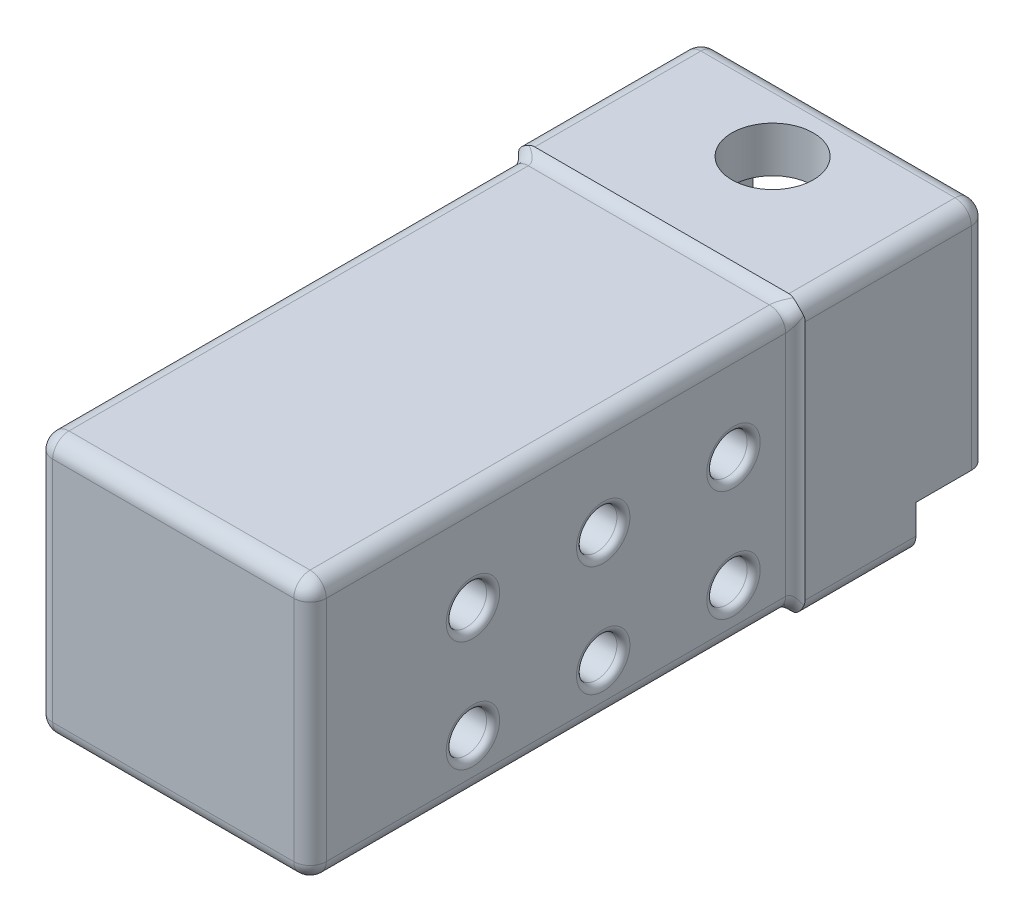
SolidWorks part; units mm, degrees
ref_plane "Front Plane" through (0, 0, 0) normal (0, 0, 1) x (1, 0, 0)
ref_plane "Top Plane" through (0, 0, 0) normal (0, 1, 0) x (1, 0, 0)
ref_plane "Right Plane" through (0, 0, 0) normal (1, 0, 0) x (0, 0, -1)
sketch "Sketch1" plane through (0, 0, 0) normal (0, 0, 1) x (1, 0, 0)
  line L0 (-4.572, -3.556) -> (4.572, -3.556)
  line L1 (-5.588, 5.334) -> (5.588, 5.334)
  line L2 (-5.588, 5.334) -> (-5.588, -5.334)
  line L3 (-5.588, -5.334) -> (5.588, -5.334)
  line L4 (5.588, 5.334) -> (5.588, -5.334)
  line L5 (-5.588, 5.334) -> (5.588, -5.334) construction
  line L6 (-5.588, -5.334) -> (5.588, 5.334) construction
  line L7 (4.572, -3.556) -> (4.572, -0.635)
  line L8 (4.572, -0.635) -> (3.556, -0.635)
  line L9 (3.556, -0.635) -> (3.556, 3.556)
  line L10 (3.556, 3.556) -> (-3.556, 3.556)
  line L11 (-3.556, 3.556) -> (-3.556, -0.635)
  line L12 (-3.556, -0.635) -> (-4.572, -0.635)
  line L13 (-4.572, -0.635) -> (-4.572, -3.556)
  point P5 (0, 3.556)
  point P7 (0, 0)
  dimension "D1" = 1.016
  dimension "D2" = 1.778
  dimension "D3" = 1.778
  dimension "D4" = 7.112
  dimension "D5" = 4.191
  dimension "D6" = 7.112
  dimension "D7" = 9.144
extrude "Boss-Extrude1" add sketch "Sketch1" along normal blind 7.112
sketch "Sketch2" plane through (0, 5.334, 0) normal (0, 1, 0) x (1, 0, 0)
  line L1 (5.588, 0) -> (-5.588, 0) construction
  circle A0 centre (0, -2.794) radius 1.5875
  dimension "D1" = 3.175
  dimension "D2" = 2.794
extrude "Cut-Extrude1" cut sketch "Sketch2" against normal through all both and the other way through all
sketch "Sketch3" plane through (0, 0, 7.112) normal (0, 0, 1) x (1, 0, 0)
  line L1 (-5.588, 5.334) -> (5.588, 5.334)
  line L2 (-5.588, 5.334) -> (-5.588, -5.334)
  line L3 (-5.588, -5.334) -> (5.588, -5.334)
  line L4 (5.588, 5.334) -> (5.588, -5.334)
sketch "Sketch7" plane through (0, 0, 7.112) normal (0, 0, 1) x (1, 0, 0)
  line L14 (-5.334, -5.08) -> (5.334, -5.08)
  line L15 (5.334, -5.08) -> (5.334, 5.08)
  line L16 (5.334, 5.08) -> (-5.334, 5.08)
  line L17 (-5.334, 5.08) -> (-5.334, -5.08)
  line L18 (-5.334, -5.08) -> (5.334, -5.08)
  line L19 (5.334, -5.08) -> (5.334, 5.08)
  line L20 (5.334, 5.08) -> (-5.334, 5.08)
  line L21 (-5.334, 5.08) -> (-5.334, -5.08)
  dimension "D1" = 0.254
extrude "Boss-Extrude3" add sketch "Sketch7" along normal blind 19.05
sketch "Sketch9" plane through (5.334, 0, 0) normal (1, 0, 0) x (0, 0, -1)
  line L0 (-26.162, -5.08) -> (-7.112, -5.08) construction
  line L1 (-7.112, 5.334) -> (-7.112, -5.334) construction
  line L2 (-9.652, -3.048) -> (-14.732, -3.048) construction
  line L3 (-9.652, -3.048) -> (-9.652, 1.27) construction
  circle A0 centre (-9.652, -3.048) radius 0.7874
  circle A1 centre (-14.732, -3.048) radius 0.7874
  circle A2 centre (-19.812, -3.048) radius 0.7874
  circle A7 centre (-14.732, 1.27) radius 0.7874
  circle A8 centre (-19.812, 1.27) radius 0.7874
  circle A13 centre (-9.652, 1.27) radius 0.7874
  dimension "D1" = 1.5748
  dimension "D2" = 2.032
  dimension "D3" = 2.54
  dimension "D7" = 5.08
  dimension "D8" = 4.318
  dimension "D4" = 3
  dimension "D5" = 2
extrude "Cut-Extrude2" cut sketch "Sketch9" against normal through all
fillet "Fillet1" radius 0.635 7 edges at (0, 5.08, 7.112) (-5.334, 0, 7.112) (0, -5.08, 7.112) (5.334, 0, 7.112) (-5.588, 0, 0) (0, 5.334, 0) (5.588, 0, 0)
fillet "Fillet3" radius 0.635 17 edges at (-5.401, -5.147, 7.336) (5.401, -5.147, 7.336) (-5.401, 5.147, 7.336) (5.401, 5.147, 7.336) (-5.588, 5.334, 3.8735) (5.588, 5.334, 3.8735) (-5.588, -5.334, 3.8735) (5.588, -5.334, 3.8735) (-5.334, -5.08, 16.891) (5.334, -5.08, 16.891) (-5.334, 5.08, 16.891) (5.334, 5.08, 16.891) (-5.402, 5.148, 0.186) (5.402, 5.148, 0.186) (-5.402, -5.334, 0.186) (0, -5.334, 0) (5.402, -5.334, 0.186)
fillet "Fillet4" radius 0.635 2 edges at (-3.556, -0.635, 3.556) (3.556, -0.635, 3.556)
fillet "Fillet5" radius 0.635 8 edges at (5.148, 4.894, 26.162) (5.334, 0, 26.162) (5.148, -4.894, 26.162) (0, -5.08, 26.162) (-5.148, -4.894, 26.162) (-5.334, 0, 26.162) (-5.148, 4.894, 26.162) (0, 5.08, 26.162)
sketch "Sketch10" plane through (0, 0, 0) normal (0, 0, -1) x (-1, 0, 0)
  line L0 (-5.588, 5.334) -> (-5.588, -5.334) construction
  line L1 (-5.588, -3.556) -> (5.588, -3.556)
  line L2 (-5.588, -3.556) -> (-5.588, -5.334)
  line L3 (-5.588, -5.334) -> (5.588, -5.334)
  line L4 (5.588, -3.556) -> (5.588, -5.334)
extrude "Cut-Extrude3" cut sketch "Sketch10" against normal blind 2.794
fillet "Fillet6" radius 0.254 12 edges at (-5.334, -2.2606, 9.652) (-5.334, 2.0574, 9.652) (-5.334, 2.0574, 14.732) (-5.334, -2.2606, 14.732) (-5.334, -2.2606, 19.812) (-5.334, 2.0574, 19.812) (5.334, -3.048, 8.8646) (5.334, 1.27, 8.8646) (5.334, -3.048, 13.9446) (5.334, -3.048, 19.0246) (5.334, 1.27, 13.9446) (5.334, 1.27, 19.0246)
